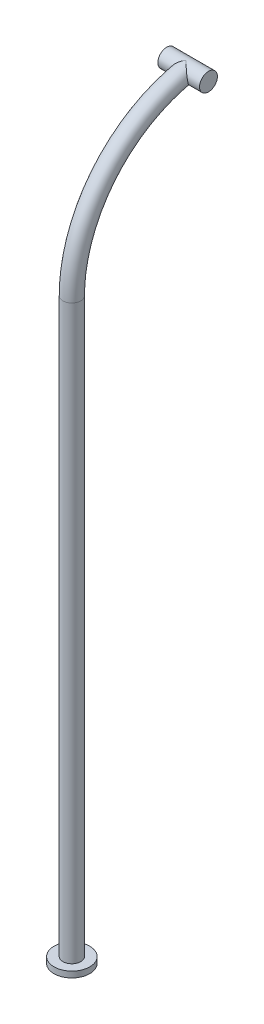
SolidWorks part; units mm, degrees
material "Nylon 101"
ref_plane "Front Plane" through (0, 0, 0) normal (0, 0, 1) x (1, 0, 0)
ref_plane "Top Plane" through (0, 0, 0) normal (0, 1, 0) x (1, 0, 0)
ref_plane "Right Plane" through (0, 0, 0) normal (1, 0, 0) x (0, 0, -1)
sketch "Sketch1" plane through (0, 0, 0) normal (0, 1, 0) x (1, 0, 0)
  circle A0 centre (0, 0) radius 1.5
extrude "Boss-Extrude1" add sketch "Sketch1" along normal blind 96
sketch "Sketch4" plane through (0, 0, 0) normal (0, -1, 0) x (1, 0, 0)
  circle A0 centre (0, 0) radius 3
extrude "Boss-Extrude4" add sketch "Sketch4" along normal blind 1
sketch "Sketch7" plane through (0, 96, 0) normal (0, 1, 0) x (1, 0, 0)
  line L0 (0, 0) -> (0, 44.3626) construction
  line L1 (0, 44.3626) -> (0, 23.5) construction
  line L2 (0, 23.5) -> (-42.5101, 23.5) construction
  line L3 (-42.5101, 23.5) -> (39.1951, 23.5) construction
  circle A0 centre (0, 0) radius 1.5
  dimension "D1" = 23.5
revolve "Revolve1" add sketch "Sketch7" angle 80 about L3 reverse direction yes
sketch "Sketch8" plane through (0, 0, 0) normal (1, 0, 0) x (0, 0, -1)
  line L0 (19.6797, 117.6658) -> (19.1588, 120.6202) construction
  circle A0 centre (19.4193, 119.143) radius 1.5
extrude "Boss-Extrude5" add sketch "Sketch8" along normal blind 3.5 and the other way blind 3.5
equation "\"4.5.00mm\"=10"
